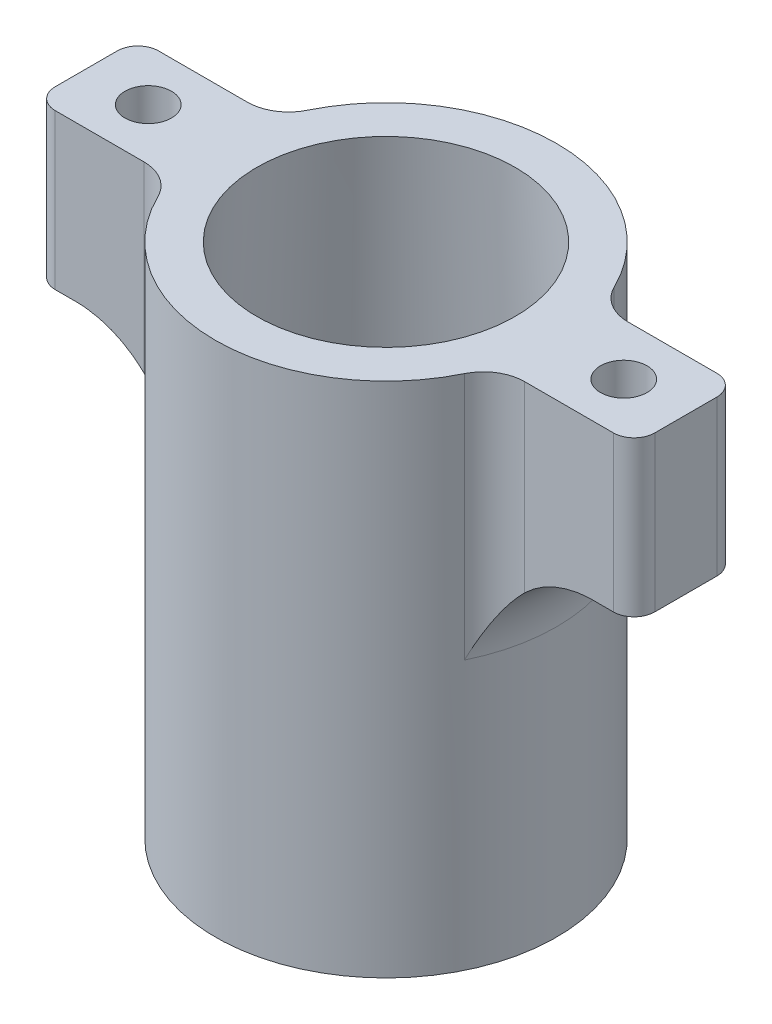
SolidWorks part; units mm, degrees
ref_plane "Front Plane" through (0, 0, 0) normal (0, 0, 1) x (1, 0, 0)
ref_plane "Top Plane" through (0, 0, 0) normal (0, 1, 0) x (1, 0, 0)
ref_plane "Right Plane" through (0, 0, 0) normal (1, 0, 0) x (0, 0, -1)
sketch "Sketch2" plane through (0, 0, 0) normal (0, 0, 1) x (1, 0, 0)
  line L0 (0, -16.7348) -> (0, 28.819) construction
  line L1 (15.5, 0) -> (16.5, 0)
  line L2 (16.5, 0) -> (16.5, 50)
  line L3 (16.5, 50) -> (12.5, 50)
  line L4 (12.5, 50) -> (15.5, 0)
  dimension "D1" = 12.5
  dimension "D2" = 15.5
  dimension "D3" = 1
  dimension "D4" = 50
revolve "Revolve1" add sketch "Sketch2" angle 360 about L0
sketch "Sketch4" plane through (0, 50, 0) normal (0, 1, 0) x (1, 0, 0)
  line L0 (-29, 0) -> (22.1896, 0) construction
  line L1 (-29, 5) -> (-29, -5)
  line L2 (-29, -5) -> (-15.7242, -5)
  line L3 (-29, 5) -> (-15.7242, 5)
  line L4 (0, -16.5) -> (0, 16.5) construction
  line L5 (29, 5) -> (15.7242, 5)
  line L6 (29, 5) -> (29, -5)
  line L7 (29, -5) -> (15.7242, -5)
  circle A0 centre (0, 0) radius 16.5 construction
  arc A1 (15.7242, -5) -> (15.7242, 5) centre (0, 0) ccw
  arc A2 (-15.7242, 5) -> (-15.7242, -5) centre (0, 0) ccw
  dimension "D1" = 5
  dimension "D2" = 29
extrude "Boss-Extrude1" add sketch "Sketch4" against normal blind 15
sketch "Sketch5" plane through (0, 50, 0) normal (0, 1, 0) x (1, 0, 0)
  line L0 (29, 0) -> (-29, 0) construction
  line L1 (29, -5) -> (29, 5) construction
  line L2 (-29, 5) -> (-29, -5) construction
  line L3 (0, -16.5) -> (0, 16.5) construction
  circle A0 centre (23, 0) radius 2.25
  arc A1 (-15.7242, -5) -> (15.7242, -5) centre (0, 0) ccw construction
  arc A2 (15.7242, 5) -> (-15.7242, 5) centre (0, 0) ccw construction
  circle A3 centre (-23, 0) radius 2.25
  dimension "D1" = 4.5
  dimension "D2" = 23
extrude "Cut-Extrude2" cut sketch "Sketch5" against normal through all
fillet "Fillet1" radius 4 4 edges at (-15.7242, 42.5, 5) (-15.7242, 42.5, -5) (15.7242, 42.5, 5) (15.7242, 42.5, -5)
fillet "Fillet2" radius 2 4 edges at (29, 42.5, 5) (29, 42.5, -5) (-29, 42.5, -5) (-29, 42.5, 5)
fillet "Fillet3" radius 9 2 edges at (-16.5, 35, 0) (16.5, 35, 0)
sketch "Sketch7" plane through (0, 50, 0) normal (0, 1, 0) x (1, 0, 0)
  line L0 (0, 16.5) -> (0, -16.5) construction
  circle A0 centre (-23, 0) radius 3.25
  arc A1 (14.8248, 7.2439) -> (-14.8248, 7.2439) centre (0, 0) ccw construction
  arc A2 (-14.8248, -7.2439) -> (14.8248, -7.2439) centre (0, 0) ccw construction
  circle A3 centre (23, 0) radius 3.25
  dimension "D1" = 6.5
extrude "Cut-Extrude4" cut sketch "Sketch7" against normal through all from offset 12 offset against normal yes
